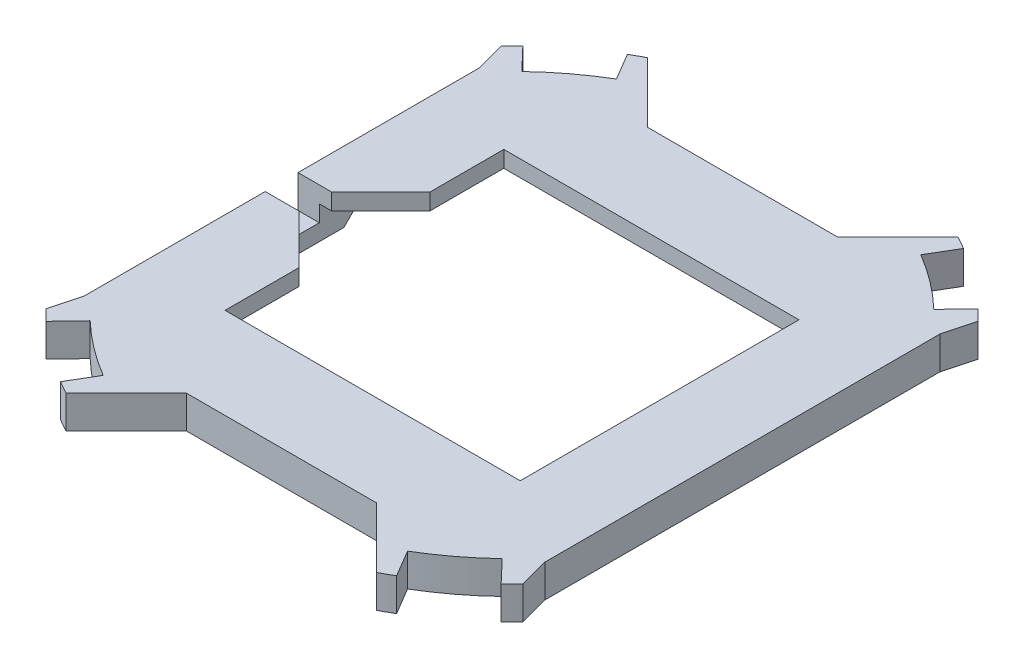
SolidWorks part; units mm, degrees
ref_plane "Front Plane" through (0, 0, 0) normal (0, 0, 1) x (1, 0, 0)
ref_plane "Top Plane" through (0, 0, 0) normal (0, 1, 0) x (1, 0, 0)
ref_plane "Right Plane" through (0, 0, 0) normal (1, 0, 0) x (0, 0, -1)
ref_axis "Axis1" through (0, -14.8911, 0) along (0, -1, 0)
ref_plane "Plane1" through (0, -16.8326, 0) normal (0, 1, 0) x (1, 0, 0)
sketch "Sketch2" plane through (0, -16.8326, 0) normal (0, 1, 0) x (1, 0, 0)
  line L0 (14.05, 12.05) -> (14.05, -12.05)
  line L5 (0, 0) -> (0, 50000) construction
  line L6 (0, 0) -> (-50000, 0) construction
  line L7 (0, 0) -> (-34510.0347, 36154.8798) construction
  line L9 (0, 0) -> (-25490.9405, 42988.7279) construction
  line L10 (14.5384, 13.8727) -> (14.05, 12.05)
  line L11 (-13.5519, 22.8543) -> (-12.5318, 21.134) construction
  line L12 (-16.9647, 17.7733) -> (-18.3456, 19.22) construction
  line L13 (-14.5384, 13.8727) -> (-14.05, 12.05)
  line L15 (-9.5538, 15.7196) -> (-10.3189, 17.0099)
  line L16 (-13.5914, 14.5289) -> (-12.5557, 13.4438)
  line L17 (-9.5538, 15.7196) -> (-10.3189, 17.0099) construction
  line L18 (-13.5914, 14.5289) -> (-12.5557, 13.4438) construction
  line L19 (-9.4725, 17.7225) -> (-5.8, 14.05)
  line L20 (13.8749, 14.5362) -> (12.563, 13.1618)
  line L21 (-9.2803, 15.6506) -> (-10.2494, 17.2848)
  line L22 (-13.8749, 14.5362) -> (-12.563, 13.1618)
  line L23 (-9.2803, 15.6506) -> (-10.2494, 17.2848)
  line L24 (-13.8749, 14.5362) -> (-12.563, 13.1618)
  line L25 (9.2803, 15.6506) -> (10.2494, 17.2848)
  line L26 (9.4725, 17.7225) -> (5.8, 14.05)
  line L27 (-12.55, -12.55) -> (-12.55, 12.55) construction
  line L28 (-12.55, 12.55) -> (12.55, 12.55) construction
  line L29 (-14.05, 12.05) -> (-14.05, -12.05)
  line L30 (-5.8, 14.05) -> (5.8, 14.05)
  line L31 (-12.55, -12.55) -> (-12.55, 12.55) construction
  line L32 (-14.5384, -13.8727) -> (-14.05, -12.05)
  line L33 (-9.2803, -15.6506) -> (-10.2494, -17.2848)
  line L34 (-13.8749, -14.5362) -> (-12.563, -13.1618)
  line L35 (-9.4725, -17.7225) -> (-5.8, -14.05)
  line L36 (-5.8, -14.05) -> (5.8, -14.05)
  line L37 (9.4725, -17.7225) -> (5.8, -14.05)
  line L38 (9.2803, -15.6506) -> (10.2494, -17.2848)
  line L39 (13.8749, -14.5362) -> (12.563, -13.1618)
  line L40 (14.5384, -13.8727) -> (14.05, -12.05)
  arc A0 (-9.4725, 17.7225) -> (-14.5384, 13.8727) centre (0, 0) ccw
  arc A2 (-10.3189, 17.0099) -> (-13.5914, 14.5289) centre (0, 0) ccw
  arc A3 (-9.5538, 15.7196) -> (-12.5557, 13.4438) centre (0, 0) ccw
  arc A4 (-10.3189, 17.0099) -> (-13.5914, 14.5289) centre (0, 0) ccw construction
  arc A5 (-9.5538, 15.7196) -> (-12.5557, 13.4438) centre (0, 0) ccw construction
  arc A6 (9.4725, 17.7225) -> (14.5384, 13.8727) centre (0, 0) cw
  arc A7 (9.2803, 15.6506) -> (12.563, 13.1618) centre (0, 0) cw
  arc A8 (-10.2494, 17.2848) -> (-13.8749, 14.5362) centre (0, 0) ccw
  arc A9 (-9.2803, 15.6506) -> (-12.563, 13.1618) centre (0, 0) ccw
  arc A10 (-10.2494, 17.2848) -> (-13.8749, 14.5362) centre (0, 0) ccw
  arc A11 (-9.2803, 15.6506) -> (-12.563, 13.1618) centre (0, 0) ccw
  arc A12 (10.2494, 17.2848) -> (13.8749, 14.5362) centre (0, 0) cw
  arc A13 (-9.2803, -15.6506) -> (-12.563, -13.1618) centre (0, 0) cw
  arc A14 (-10.2494, -17.2848) -> (-13.8749, -14.5362) centre (0, 0) cw
  arc A15 (-9.4725, -17.7225) -> (-14.5384, -13.8727) centre (0, 0) cw
  arc A16 (9.2803, -15.6506) -> (12.563, -13.1618) centre (0, 0) ccw
  arc A17 (10.2494, -17.2848) -> (13.8749, -14.5362) centre (0, 0) ccw
  arc A18 (9.4725, -17.7225) -> (14.5384, -13.8727) centre (0, 0) ccw
  point P0 (0, 0)
  point P47 (0, 14.05)
  point P62 (-14.05, 0)
  point P67 (14.05, 0)
  dimension "D1" = 1.5
  dimension "D4" = 1.5
  dimension "D6" = 135
  dimension "D7" = 0.5
  dimension "D8" = 6.75
  dimension "D9" = 165
  dimension "D2" = 0
  dimension "D3" = 0.2
extrude "Boss-Extrude3" add sketch "Sketch2" along normal blind 1 and the other way blind 1 contours L37 A18 L38 A16 L39 L40 L0 L10 A6 L20 A7 L25 L26 L30 L19 A0 L23 A11 L24 L13 L29 L32 A15 L34 A13 L33 L35 L36 region at (0, -16.8326, 0)
sketch "Sketch3" plane through (0, -16.8326, 0) normal (0, 1, 0) x (1, 0, 0)
  line L0 (12.55, -12.55) -> (-12.55, -12.55) construction
  line L1 (12.55, 12.55) -> (12.55, -12.55) construction
  line L2 (-12.55, -12.55) -> (-12.55, 12.55) construction
  line L3 (-12.55, 12.55) -> (12.55, 12.55) construction
  line L4 (12.55, -12.55) -> (-12.55, -12.55) construction
  line L5 (12.55, 12.55) -> (12.55, -12.55) construction
  line L6 (-12.55, -12.55) -> (-12.55, 12.55) construction
  line L7 (-12.55, 12.55) -> (12.55, 12.55) construction
  line L8 (-8, 7.5) -> (8, 7.5) construction
  line L9 (8, -7.5) -> (-8, -7.5) construction
  line L10 (-8, 7.5) -> (-8, 1.5) construction
  line L11 (-8, -1.5) -> (-8, -7.5) construction
  line L12 (8, 7.5) -> (8, -7.5) construction
  line L13 (-8, 7.5) -> (-8, 1.5) construction
  line L14 (-8, -1.5) -> (-8, -7.5) construction
  line L15 (-8, 7.5) -> (8, 7.5) construction
  line L16 (8, 7.5) -> (8, -7.5) construction
  line L17 (8, -7.5) -> (-8, -7.5) construction
  line L18 (-12.75, 12.75) -> (12.75, 12.75)
  line L19 (-9, -8.5) -> (9, -8.5)
  line L20 (-9, -8.5) -> (-9, 8.5)
  line L21 (-9, 8.5) -> (9, 8.5)
  line L22 (9, -8.5) -> (9, 8.5)
  line L23 (-9, -8.5) -> (9, 8.5) construction
  line L24 (-9, 8.5) -> (9, -8.5) construction
  line L25 (12.75, 12.75) -> (12.75, -12.75)
  line L26 (12.75, -12.75) -> (-12.75, -12.75)
  line L27 (-12.75, -12.75) -> (-12.75, 12.75)
  point P3 (0, 0)
  dimension "D1" = 1
  dimension "D2" = 1
  dimension "D3" = 0.2
extrude "Cut-Extrude1" cut sketch "Sketch3" along normal through all contours L19 L22 L21 L20 region at (0, -16.8326, 0)
extrude "Cut-Extrude3" cut sketch "Sketch3<4>" against normal through all contours L19 L22 L21 L20 | L27 L26 L25 L18 L22 L19 L20 L21 region at (0, -16.8326, -12.3894) region at (0, -16.8326, 0)
sketch "Sketch3<4>" plane through (0, -16.8326, 0) normal (0, 1, 0) x (1, 0, 0) same geometry as "Sketch3"
sketch "Sketch4" plane through (0, -16.8326, 0) normal (0, 1, 0) x (1, 0, 0)
  line L0 (0, 0) -> (-50000, 0) construction
  line L2 (-5.8445, -1) -> (-21.8445, -1)
  line L3 (-5.8445, -1) -> (-5.8445, 1)
  line L4 (-5.8445, 1) -> (-21.8445, 1)
  line L5 (-21.8445, -1) -> (-21.8445, 1)
  line L6 (-5.8445, -1) -> (-21.8445, 1) construction
  line L7 (-5.8445, 1) -> (-21.8445, -1) construction
  point P3 (-13.8445, 0)
  dimension "D1" = 16
  dimension "D2" = 2
extrude "Cut-Extrude4" cut sketch "Sketch4" against normal through all both and the other way through all
chamfer "Chamfer1" distance 3 angle 45 2 edges at (-9, -16.3326, -1) (-9, -16.3326, 1)
sketch "Sketch6" plane through (-14.05, 0, 0) normal (-1, 0, 0) x (0, 0, 1)
  line L0 (0, 0) -> (0, -50000) construction
  line L2 (-2.5, -17.8326) -> (2.5, -17.8326)
  line L3 (-2.5, -17.8326) -> (-2.5, -18.8326)
  line L4 (-2.5, -18.8326) -> (2.5, -18.8326)
  line L6 (-1, -15.8326) -> (-1, -17.8326) construction
  line L7 (2.5, -17.8326) -> (2.5, -18.8326)
  line L8 (-12.05, -17.8326) -> (-1, -17.8326) construction
  point P12 (0, -17.8326)
  point P13 (0, -18.8326)
  dimension "D1" = 1.5
  dimension "D2" = 1
extrude "Boss-Extrude5" add sketch "Sketch6" against normal up to surface (1.3 mm away) up to face at (-12.75, -17.3326, -6.875)
chamfer "Chamfer2" distance 1 angle 45 2 edges at (-13.4, -17.8326, 2.5) (-13.4, -17.8326, -2.5)
